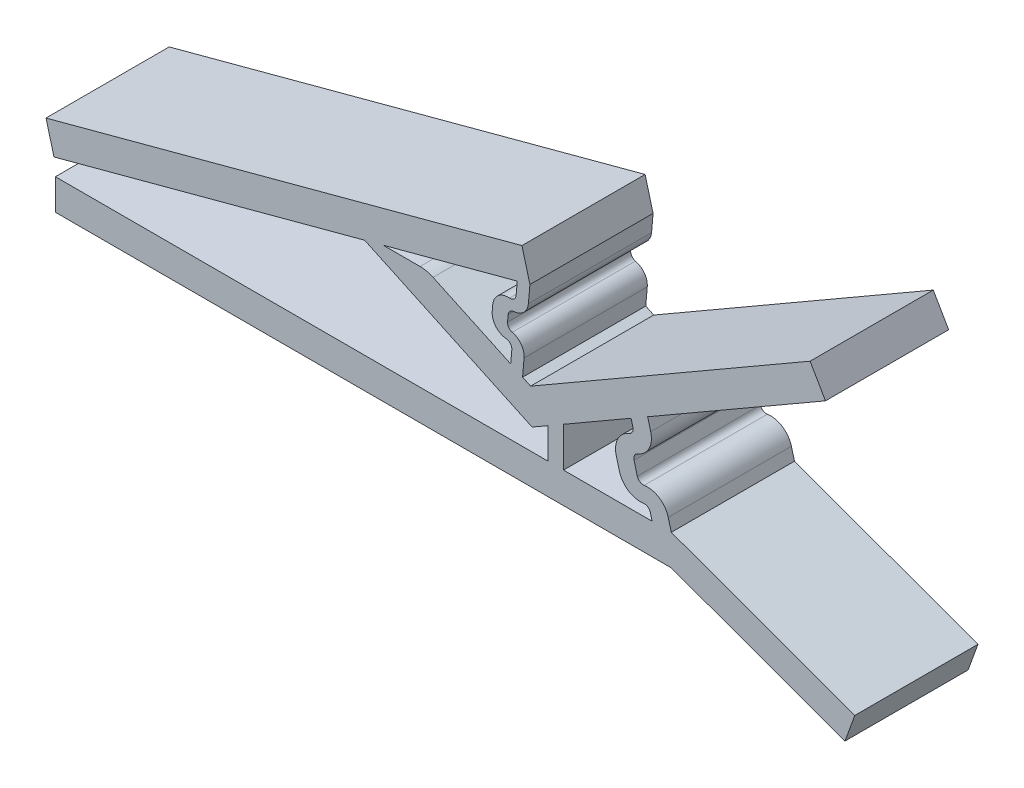
SolidWorks part; units mm, degrees
ref_plane "Front Plane" through (0, 0, 0) normal (0, 0, 1) x (1, 0, 0)
ref_plane "Top Plane" through (0, 0, 0) normal (0, 1, 0) x (1, 0, 0)
ref_plane "Right Plane" through (0, 0, 0) normal (1, 0, 0) x (0, 0, -1)
sketch "Sketch3" plane through (0, 0, 0) normal (0, 0, 1) x (1, 0, 0)
  line L0 (0, 0) -> (100, 0)
  line L1 (100, 0) -> (100, 5)
  line L2 (100, 5) -> (0, 5)
  line L3 (0, 5) -> (0, 0)
  line L4 (100, 0) -> (128.1908, -10.2606)
  line L5 (128.1908, -10.2606) -> (129.7977, -5.8455)
  line L6 (129.7977, -5.8455) -> (100, 5)
  line L7 (82.5, 5) -> (82.5, 11.4434)
  line L8 (77.4019, 8.5) -> (125.0333, 36)
  line L9 (80, 10) -> (80, 5)
  line L10 (77.4019, 8.5) -> (71.3397, 5) construction
  line L11 (125.0333, 36) -> (122.5333, 40.3301)
  line L12 (122.5333, 40.3301) -> (77.156, 14.1315)
  line L13 (77.156, 14.1315) -> (57.7263, 23.1918) construction
  line L14 (77.0448, 28.3682) -> (75.7507, 33.1978)
  line L15 (50.2127, 21.1785) -> (77.4019, 8.5)
  line L16 (71.3397, 5) -> (130.2116, 20.7747) construction
  line L17 (90.154, 14.7) -> (92.4833, 6.0067)
  line L18 (92.4833, 6.0067) -> (96.347, 7.0419)
  line L19 (96.347, 7.0419) -> (96.8942, 5)
  line L20 (90.154, 14.7) -> (94.0177, 15.7353)
  line L21 (94.0177, 15.7353) -> (93.4705, 17.7772)
  line L22 (96.1603, 19.3301) -> (97.5625, 14.0969)
  line L23 (97.5625, 14.0969) -> (93.6988, 13.0616)
  line L24 (93.6988, 13.0616) -> (94.7341, 9.1979)
  line L25 (94.7341, 9.1979) -> (98.5978, 10.2332)
  line L26 (98.5978, 10.2332) -> (100, 5)
  line L27 (-0.2293, 7.6627) -> (77.0448, 28.3682)
  line L28 (57.7263, 23.1918) -> (88.227, 20.5233) construction
  line L29 (75.7507, 33.1978) -> (-1.5234, 12.4923)
  line L30 (-1.5234, 12.4923) -> (-0.2293, 7.6627)
  line L31 (71.231, 25.0218) -> (70.7081, 19.0446)
  line L32 (70.7081, 19.0446) -> (74.1947, 18.7395)
  line L33 (74.1947, 18.7395) -> (73.9235, 15.6389)
  line L34 (74.9889, 27.8173) -> (74.7177, 24.7167)
  line L35 (74.7177, 24.7167) -> (71.231, 25.0218)
  line L36 (76.5793, 23.0481) -> (77.0448, 28.3682)
  line L37 (76.5793, 23.0481) -> (73.5907, 23.3096)
  line L38 (73.5907, 23.3096) -> (73.3293, 20.321)
  line L39 (73.3293, 20.321) -> (76.3179, 20.0595)
  line L40 (76.3179, 20.0595) -> (75.8524, 14.7394)
  line L41 (53.2181, 21.9838) -> (60.3167, 21.9838)
  line L42 (60.3167, 21.9838) -> (77.156, 14.1315)
  point P28 (94.2164, 11.1298)
  point P44 (70.9695, 22.0332)
  point P49 (73.46, 21.8153)
  dimension "D1" = 100
  dimension "D2" = 30
  dimension "D3" = 5
  dimension "D4" = 160
  dimension "D5" = 5
  dimension "D6" = 2.5
  dimension "D7" = 30
  dimension "D8" = 20
  dimension "D9" = 3
  dimension "D10" = 55
  dimension "D11" = 5
  dimension "D12" = 5
  dimension "D13" = 30
  dimension "D14" = 125
  dimension "D15" = 15
  dimension "D16" = 3
  dimension "D17" = 2.5
  dimension "D18" = 3
  dimension "D19" = 2.5
  dimension "D20" = 4
  dimension "D21" = 3
  dimension "D22" = 4
  dimension "D23" = 20
  dimension "D24" = 40
  dimension "D25" = 5
  dimension "D26" = 20
  dimension "D27" = 3
  dimension "D28" = 6
  dimension "D29" = 2.5
  dimension "D30" = 2
  dimension "D31" = 3
  dimension "D32" = 2
  dimension "D33" = 80
extrude "Boss-Extrude3" add sketch "Sketch3" along normal blind 20 contours L5 L6 L1 L4 | L2 L3 L0 L1 | L26 L25 L24 L23 L22 L8 L21 L20 L17 L18 L19 L2 | L8 L9 L2 L7 | L42 L41 L27 L15 L8 L11 L12 | L33 L42 L40 L39 L38 L37 L36 L27 L34 L35 L31 L32 | L29 L30 L27 L14 region at (50, 2.5, 0) region at (114.5008, -2.7548, 0) region at (98.4471, 5.1739, 0) region at (81.3026, 7.876, 0) region at (78.2944, 9.9542, 0) region at (37.7607, 20.4302, 0) region at (76.0558, 27.9476, 0)
fillet "Fillet2" radius 3.5 2 edges at (92.4833, 6.0067, 10) (90.154, 14.7, 10)
fillet "Fillet3" radius 3.5 2 edges at (98.5978, 10.2332, 10) (97.5625, 14.0969, 10)
fillet "Fillet4" radius 1 4 edges at (96.347, 7.0419, 10) (94.0177, 15.7353, 10) (93.6988, 13.0616, 10) (94.7341, 9.1979, 10)
fillet "Fillet5" radius 5 1 edges at (60.3167, 21.9838, 10)
fillet "Fillet6" radius 2.5 4 edges at (70.7081, 19.0446, 10) (71.231, 25.0218, 10) (76.5793, 23.0481, 10) (76.3179, 20.0595, 10)
fillet "Fillet7" radius 1 4 edges at (74.1947, 18.7395, 10) (74.7177, 24.7167, 10) (73.5907, 23.3096, 10) (73.3293, 20.321, 10)
